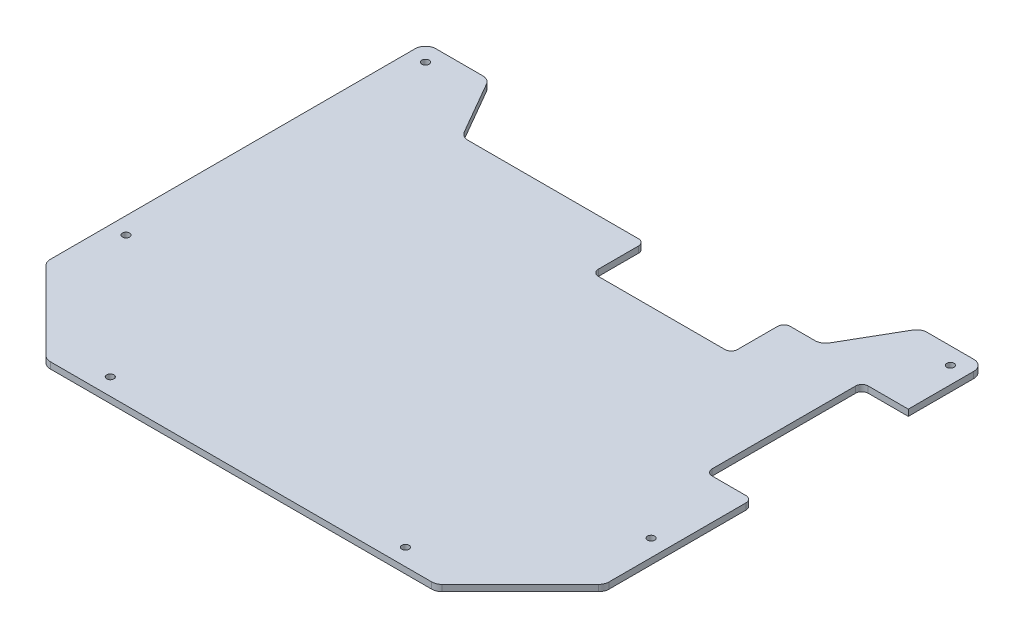
SolidWorks part; units mm, degrees
material "Acier non allié"
ref_plane "Front" through (0, 0, 0) normal (0, 0, 1) x (1, 0, 0)
ref_plane "Top" through (0, 0, 0) normal (0, 1, 0) x (1, 0, 0)
ref_plane "Right" through (0, 0, 0) normal (1, 0, 0) x (0, 0, -1)
sketch "Esquisse1" plane through (0, 0, 0) normal (0, 1, 0) x (1, 0, 0)
  line L0 (0, 0) -> (0, 190) construction
  line L1 (-92.5, 0) -> (92.5, 0)
  line L2 (92.5, 0) -> (132.5, 40)
  line L3 (132.5, 40) -> (132.5, 220)
  line L4 (132.5, 220) -> (102.5, 220)
  line L5 (102.5, 220) -> (85.1795, 190)
  line L6 (85.1795, 190) -> (-85.1795, 190)
  line L7 (-102.5, 220) -> (-85.1795, 190)
  line L8 (-132.5, 220) -> (-102.5, 220)
  line L9 (-132.5, 40) -> (-132.5, 220)
  line L10 (-92.5, 0) -> (-132.5, 40)
  dimension "D1" = 132.5
  dimension "D2" = 220
  dimension "D3" = 60
  dimension "D4" = 30
  dimension "D5" = 40
  dimension "D6" = 40
  dimension "D7" = 30
extrude "Boss.-Extru.1" add sketch "Esquisse1" along normal blind 3
fillet "Congé1" radius 5 10 edges at (92.5, 1.5, 0) (132.5, 1.5, -40) (132.5, 1.5, -220) (102.5, 1.5, -220) (85.1795, 1.5, -190) (-85.1795, 1.5, -190) (-102.5, 1.5, -220) (-132.5, 1.5, -220) (-92.5, 1.5, 0) (-132.5, 1.5, -40)
sketch "Esquisse2" plane through (0, 3, 0) normal (0, 1, 0) x (1, 0, 0)
  line L0 (0, 0) -> (0, 294.1173) construction
  line L2 (-90.4289, 0) -> (90.4289, 0) construction
  circle A0 centre (70, 8) radius 1
  circle A1 centre (124.5, 70) radius 1
  circle A2 centre (124.5, 212) radius 1
  circle A3 centre (-124.5, 212) radius 1
  circle A4 centre (-124.5, 70) radius 1
  circle A5 centre (-70, 8) radius 1
  point P15 (0, 0)
  point P17 (65.338, 0)
  dimension "D2" = 2
  dimension "D6" = 2
  dimension "D9" = 2
  dimension "D1" = 70
  dimension "D3" = 8
  dimension "D4" = 124.5
  dimension "D5" = 70
  dimension "D7" = 124.5
  dimension "D8" = 212
extrude "Enlèv. mat.-Extru.1" cut sketch "Esquisse2" against normal blind 3
hole_wizard "Dégagement M31" positions "Esquisse3" profile "Esquisse4" hole size "M3" standard "ISO" end condition through all
sketch "Esquisse3" plane through (0, 3, 0) normal (0, 1, 0) x (1, 0, 0)
  point P0 (70, 8)
  point P3 (-70, 8)
  point P6 (-124.5, 70)
  point P9 (-124.5, 212)
  point P12 (124.5, 212)
  point P15 (124.5, 70)
sketch "Esquisse4" plane through (70, 3, -8) normal (1, 0, 0) x (0, 0, 1)
  line L0 (0, 0) -> (0, 3)
  line L1 (0, 3) -> (1.7, 3)
  line L2 (1.7, 3) -> (1.7, 0)
  line L5 (1.7, 0) -> (0, 0)
  line L11 (0, -6.35) -> (0, 107.95) construction
  dimension "Diamètre du perçage jusqu'au prochain" = 3.4
  dimension "Profondeur du perçage jusqu'au prochain" = 3
sketch "Esquisse5" plane through (0, 3, 0) normal (0, 1, 0) x (1, 0, 0)
  line L0 (82.2927, 190) -> (-82.2927, 190) construction
  line L1 (67.5, 190) -> (1.5, 190)
  line L2 (67.5, 190) -> (67.5, 165)
  line L3 (67.5, 165) -> (1.5, 165)
  line L4 (1.5, 190) -> (1.5, 165)
  line L5 (132.5, 42.0711) -> (132.5, 215) construction
  line L6 (132.5, 184) -> (110.5, 184)
  line L7 (132.5, 184) -> (132.5, 110)
  line L8 (132.5, 110) -> (110.5, 110)
  line L9 (110.5, 184) -> (110.5, 110)
  line L10 (127.5, 220) -> (105.3868, 220) construction
  dimension "D1" = 25
  dimension "D2" = 65
  dimension "D3" = 131
  dimension "D4" = 36
  dimension "D5" = 110
  dimension "D6" = 22
extrude "Enlèv. mat.-Extru.2" cut sketch "Esquisse5" against normal through all
fillet "Congé2" radius 3 7 edges at (132.5, 1.5, -110) (110.5, 1.5, -110) (110.5, 1.5, -184) (67.5, 1.5, -190) (67.5, 1.5, -165) (1.5, 1.5, -165) (1.5, 1.5, -190)
equation "\"WIDTH\"= 300mm'Total width of the robot"
equation "\"LENGTH\"= 220mm'Total length of the robot"
equation "\"CUT_DEPTH\"= 45mm'Depth of the cut on the edges of the plate"
equation "\"Plate_th\"= 3mm'Thickness of the plate"
equation "\"D1\"= \"Plate_th\""
